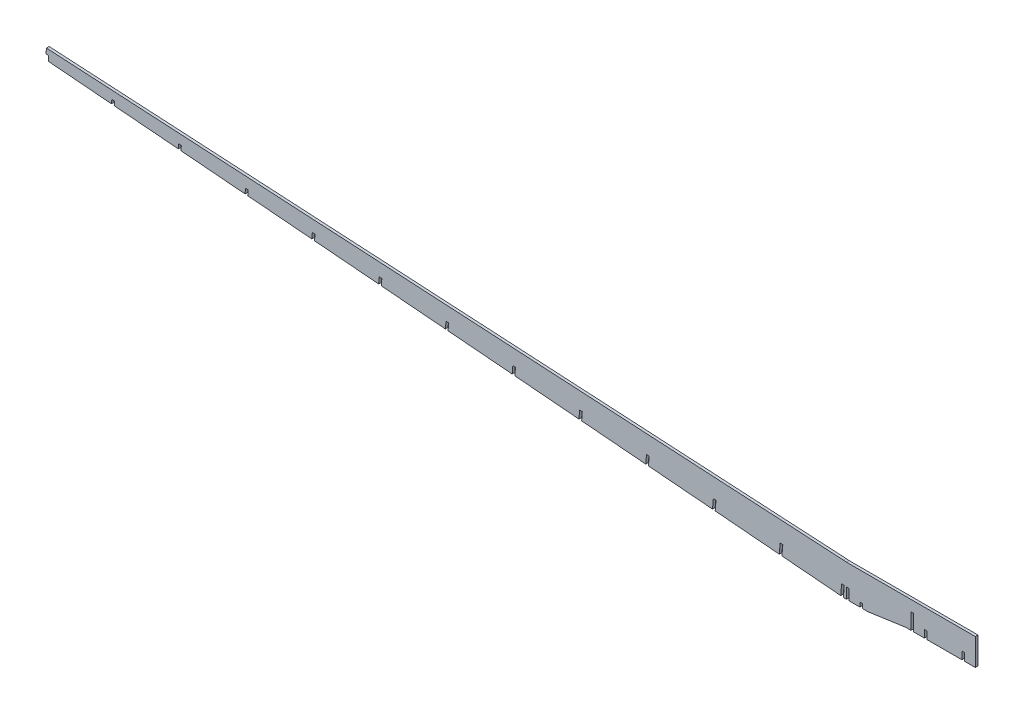
SolidWorks part; units mm, degrees
material "Plywood"
ref_plane "Front Plane" through (0, 0, 0) normal (0, 0, 1) x (1, 0, 0)
ref_plane "Top Plane" through (0, 0, 0) normal (0, 1, 0) x (1, 0, 0)
ref_plane "Right Plane" through (0, 0, 0) normal (1, 0, 0) x (0, 0, -1)
sketch "Sketch1" plane through (0, 0, 0) normal (0, 0, 1) x (1, 0, 0)
  line L0 (76.2, 56.7475) -> (76.2, 37.6975)
  line L1 (79.375, 56.7475) -> (79.375, 37.6975)
  line L2 (0, 44.0475) -> (0, 31.3475)
  line L3 (3.175, 44.0475) -> (3.175, 31.3475)
  line L4 (-5.7133, 44.4467) -> (-6.776, 31.7912)
  line L5 (-2.5494, 44.181) -> (-3.6121, 31.5255)
  line L6 (-1.4923, 31.3475) -> (25.4, 31.3475)
  line L7 (25.4, 31.3475) -> (69.85, 37.6975)
  line L8 (-2.5494, 44.181) -> (-0.424, 69.4919) construction
  line L9 (-0.424, 69.4919) -> (-3.5879, 69.7576)
  line L10 (-3.5879, 69.7576) -> (-5.7133, 44.4467) construction
  line L11 (-5.7133, 44.4467) -> (-2.5494, 44.181)
  line L12 (3.175, 44.0475) -> (3.175, 69.4475) construction
  line L13 (3.175, 69.4475) -> (0, 69.4475)
  line L14 (0, 69.4475) -> (0, 44.0475) construction
  line L15 (0, 44.0475) -> (3.175, 44.0475)
  line L16 (92.075, 37.6975) -> (92.075, 46.5875)
  line L17 (-942.8808, 122.7744) -> (-947.5199, 67.5279)
  line L18 (0, 69.4475) -> (-0.424, 69.4919)
  line L19 (3.175, 69.4475) -> (152.4, 69.4475)
  line L20 (152.4, 69.4475) -> (152.4, 37.6975)
  line L21 (152.4, 37.6975) -> (69.85, 37.6975)
  line L22 (92.075, 46.5875) -> (95.25, 46.5875)
  line L23 (95.25, 46.5875) -> (95.25, 37.6975)
  line L24 (-1.4923, 31.3475) -> (-943.9128, 110.4848)
  line L25 (79.375, 69.4475) -> (79.375, 56.7475)
  line L26 (-942.8808, 122.7744) -> (-3.5879, 69.7576)
  line L27 (136.525, 37.6975) -> (136.525, 46.5875)
  line L28 (76.2, 69.4475) -> (76.2, 56.7475)
  line L29 (79.375, 56.7475) -> (76.2, 56.7475)
  line L30 (-943.5688, 114.5813) -> (-5.7133, 44.4467)
  line L31 (136.525, 46.5875) -> (139.7, 46.5875)
  line L32 (139.7, 46.5875) -> (139.7, 37.6975)
  line L33 (15.875, 31.3475) -> (15.875, 36.4275)
  line L34 (15.875, 36.4275) -> (19.05, 36.4275)
  line L35 (19.05, 36.4275) -> (19.05, 31.3475)
  line L36 (-942.8808, 122.7744) -> (-946.0519, 122.9534)
  line L37 (-946.0519, 122.9534) -> (-946.5835, 116.6233)
  line L38 (-946.5835, 116.6233) -> (-943.4123, 116.4443)
  dimension "D3" = 76.2
  dimension "D10" = 12.3329
  dimension "D11" = 8.2219
  dimension "D2" = 25.4
  dimension "D4" = 25.4
  dimension "D5" = 12.7
  dimension "D7" = 3.175
  dimension "D9" = 3.175
  dimension "D12" = 3.175
  dimension "D6" = 19.05
  dimension "D13" = 6.35
  dimension "D14" = 12.7
  dimension "D16" = 3.175
  dimension "D17" = 3.175
  dimension "D18" = 12.7
  dimension "D19" = 12.7
  dimension "D20" = 8.89
  dimension "D21" = 8.89
  dimension "D15" = 76.2
  dimension "D22" = 12.7
  dimension "D23" = 3.175
  dimension "D24" = 5.08
  dimension "D8" = 6.35
  dimension "D25" = 3.175
  dimension "D26" = 6.35
extrude "Boss-Extrude1" add sketch "Sketch1" along normal mid plane 3.175 contours L17 L30 L11 L5 L24 L6 L2 L15 L3 L7 L21 L0 L28 L19 L13 L18 L9 L26 | L30 L17 L24 L4 | L29 L25 L19 L28 | L19 L25 L1 L21 L20 | L37 L38 L17 L36 region at (-328.9931, 77.9728, 0) region at (77.7875, 63.0975, 0) region at (115.8875, 53.8578, 0) region at (-944.7321, 119.6988, 0) region at (-395.1618, 68.9894, 0)
sketch "Sketch2" plane through (0, 0, 1.5875) normal (0, 0, 1) x (1, 0, 0)
  line L2 (-73.2652, 73.2231) -> (-80.3969, -11.7061)
  line L3 (-943.5688, 114.5813) -> (-5.7133, 44.4467)
  line L6 (-76.4291, 73.4888) -> (-83.5608, -11.4404)
  line L7 (-6.776, 31.7912) -> (-943.9128, 110.4848)
  line L10 (-152.4177, 77.6821) -> (-159.3225, -4.5442)
  line L14 (-155.5816, 77.9478) -> (-162.4863, -4.2785)
  line L18 (-231.5658, 82.1932) -> (-238.251, 2.5812)
  line L22 (-234.7297, 82.4589) -> (-241.4149, 2.8469)
  line L26 (-310.7178, 86.6582) -> (-317.1769, 9.7387)
  line L30 (-313.8817, 86.9239) -> (-320.3408, 10.0043)
  line L34 (-389.8657, 91.1713) -> (-396.1056, 16.8623)
  line L38 (-393.0296, 91.437) -> (-399.2695, 17.128)
  line L42 (-469.0186, 95.6263) -> (-475.031, 24.0265)
  line L46 (-472.1824, 95.892) -> (-478.1948, 24.2921)
  line L50 (-548.1666, 100.1381) -> (-553.9596, 31.1506)
  line L54 (-551.3305, 100.4038) -> (-557.1235, 31.4163)
  line L58 (-627.3195, 104.5918) -> (-632.8849, 38.3152)
  line L62 (-630.4834, 104.8575) -> (-636.0488, 38.5809)
  line L66 (-706.4673, 109.1069) -> (-711.8138, 45.4365)
  line L70 (-709.6312, 109.3725) -> (-714.9777, 45.7022)
  line L74 (-785.6206, 113.5558) -> (-790.7389, 52.6041)
  line L78 (-788.7845, 113.8214) -> (-793.9027, 52.8697)
  line L82 (-864.7684, 118.071) -> (-869.6679, 59.7246)
  line L86 (-867.9323, 118.3366) -> (-872.8317, 59.9902)
  line L89 (-942.9091, 122.4365) -> (-947.5795, 66.8182)
  line M2 (-943.9128, 110.4848) -> (-6.776, 31.7912)
extrude "Cut-Extrude1" cut sketch "Sketch2" against normal through all contours L3 L6 L2 M2 | L3 L14 L7 L10 | L3 L22 L7 L18 | L3 L30 L7 L26 | L3 L38 L7 L34 | L3 L46 L7 L42 | L3 L54 L7 L50 | L3 L62 L7 L58 | L3 L70 L7 L66 | L3 L78 L7 L74 | L3 L86 L7 L82 region at (-77.3317, 43.7615, 1.5875) region at (-156.332, 50.0322, 1.5875) region at (-235.3323, 56.3029, 1.5875) region at (-314.3326, 62.5736, 1.5875) region at (-393.3328, 68.8442, 1.5875) region at (-472.3331, 75.1149, 1.5875) region at (-551.3334, 81.3856, 1.5875) region at (-630.3336, 87.6563, 1.5875) region at (-709.3339, 93.9269, 1.5875) region at (-788.334, 100.1976, 1.5875) region at (-867.3342, 106.4683, 1.5875)
move or copy body "Body-Move/Copy1" [suppressed] bodies to move or copy 102 parameters "D1"=0, "D2"=0, "D3"=0
equation "\"D11@Sketch1\"=\"D10@Sketch1\"*(2/3)"
